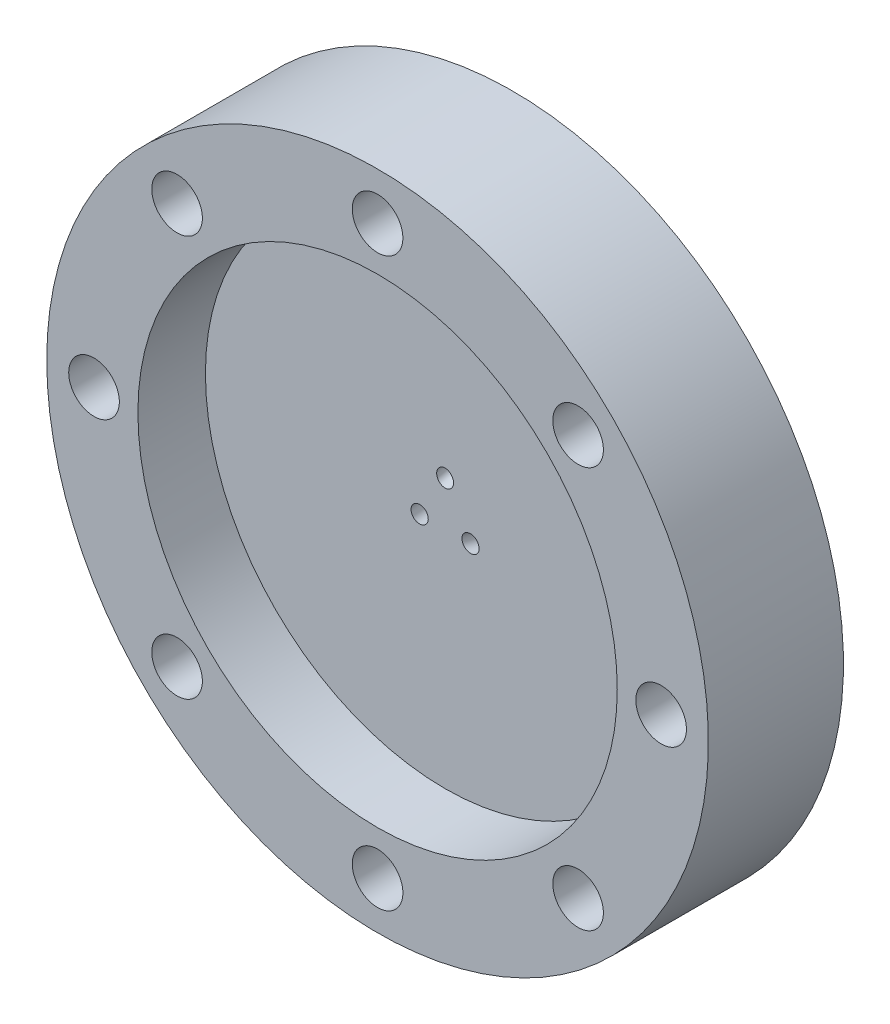
SolidWorks part; units mm, degrees
material "PLA (Polylactic Acid)"
ref_plane "Front Plane" through (0, 0, 0) normal (0, 0, 1) x (1, 0, 0)
ref_plane "Top Plane" through (0, 0, 0) normal (0, 1, 0) x (1, 0, 0)
ref_plane "Right Plane" through (0, 0, 0) normal (1, 0, 0) x (0, 0, -1)
sketch "Sketch2" plane through (0, 0, -1.7131) normal (0, 0, -1) x (-1, 0, 0)
  circle A0 centre (0, 0) radius 31.115
  dimension "D1" = 62.23
extrude "Boss-Extrude1" add sketch "Sketch2" along normal blind 12.7
sketch "Sketch3" plane through (0, 0, -14.4131) normal (0, 0, -1) x (-1, 0, 0)
  circle A0 centre (0, 26.67) radius 2.3813
  circle A1 centre (0, 0) radius 26.67 construction
  circle A2 centre (18.8585, 18.8585) radius 2.3813
  circle A4 centre (26.67, 0) radius 2.3813
  circle A5 centre (18.8585, -18.8585) radius 2.3813
  circle A6 centre (0, -26.67) radius 2.3813
  circle A7 centre (-18.8585, -18.8585) radius 2.3813
  circle A8 centre (-26.67, 0) radius 2.3813
  circle A9 centre (-18.8585, 18.8585) radius 2.3813
  point P23 (0, 0)
  dimension "D1" = 53.34
  dimension "D2" = 4.7625
  dimension "D3" = 8
extrude "Cut-Extrude3" cut sketch "Sketch3" against normal up to surface (12.7 mm away) up to face at (-31.115, 0, -1.7131)
sketch "Sketch4" plane through (0, 0, -1.7131) normal (0, 0, 1) x (1, 0, 0)
  circle A0 centre (0, 0) radius 22.5425
  dimension "D1" = 45.085
extrude "Cut-Extrude2" cut sketch "Sketch4" against normal blind 6.35
sketch "Sketch6" plane through (0, 0, 0) normal (1, 0, 0) x (0, 0, -1)
  line L0 (-69.0368, 0) -> (69.0368, 0) construction
  line L1 (9.9681, 0) -> (9.9681, 6.35)
  line L2 (9.9681, 6.35) -> (12.5081, 6.35)
  line L3 (12.5081, 6.35) -> (12.5081, 2.3812)
  line L4 (12.5081, 2.3812) -> (14.4131, 2.3812)
  line L5 (14.4131, 2.3812) -> (14.4131, 0)
  line L6 (14.4131, 0) -> (9.9681, 0)
  line L7 (14.4131, -26.67) -> (14.4131, 26.67) construction
  line L8 (1.7131, 31.115) -> (1.7131, -31.115) construction
  point P3 (8.0631, 0)
  point P5 (0, 0)
  dimension "D1" = 6.35
  dimension "D2" = 1.905
  dimension "D3" = 6.35
  dimension "D4" = 1.905
revolve "Cut-Revolve2" cut sketch "Sketch6" angle 360 about L0
sketch "Sketch7" plane through (0, 0, 0) normal (1, 0, 0) x (0, 0, -1)
  line L0 (1.7131, 0) -> (-4.6369, 0) construction
  line L1 (1.7131, 31.115) -> (1.7131, -31.115) construction
  line L2 (9.9681, 6.35) -> (9.9681, -6.35) construction
  line L3 (9.9681, 3.175) -> (-4.6369, 0) construction
  dimension "D1" = 6.35
  dimension "D2" = 3.175
ref_plane "Plane1" through (0, 0, 4.6369) normal (0, -0.2124, 0.9772) x (1, 0, 0)
sketch "Sketch8" plane through (0, 0, 4.6369) normal (0, -0.2124, 0.9772) x (1, 0, 0)
  circle A0 centre (0, 0) radius 0.7937
  dimension "D1" = 1.5875
extrude "Cut-Extrude4" cut sketch "Sketch8" against normal up to surface (14.7736 mm away) up to face at (6.35, 0, -9.9681)
pattern_circular "CirPattern1" count 3 over 360 about axis through (0, 0, -1.7131) along (0, 0, 1) of "Cut-Extrude4"
